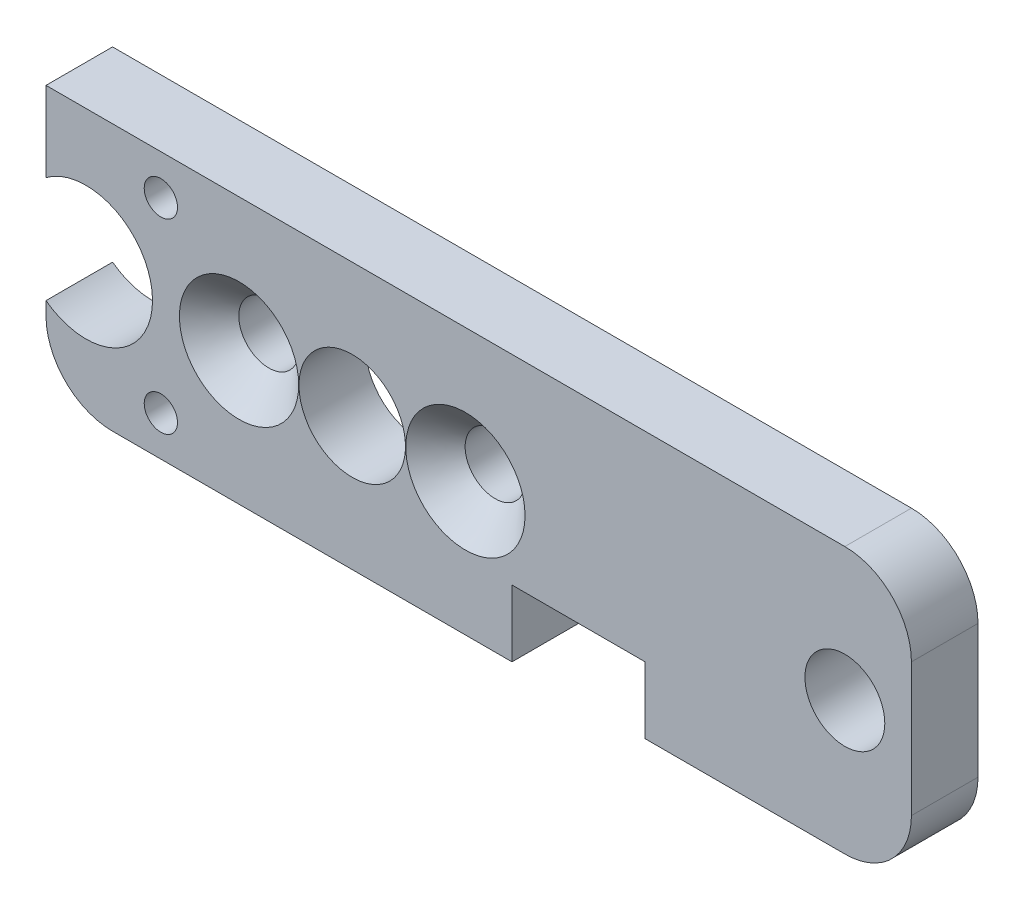
SolidWorks part; units mm, degrees
ref_plane "Front Plane" through (0, 0, 0) normal (0, 0, 1) x (1, 0, 0)
ref_plane "Top Plane" through (0, 0, 0) normal (0, 1, 0) x (1, 0, 0)
ref_plane "Right Plane" through (0, 0, 0) normal (1, 0, 0) x (0, 0, -1)
sketch "Sketch1" plane through (0, 0, 0) normal (0, 0, 1) x (1, 0, 0)
  line L1 (-27.303, 7.4194) -> (37.697, 7.4194)
  line L2 (-27.303, 7.4194) -> (-27.303, -12.5806)
  line L3 (-27.303, -12.5806) -> (37.697, -12.5806)
  line L4 (37.697, 7.4194) -> (37.697, -12.5806)
  dimension "D1" = 65
  dimension "D2" = 20
extrude "Boss-Extrude1" add sketch "Sketch1" along normal blind 5
sketch "Sketch2" plane through (0, 0, 5) normal (0, 0, 1) x (1, 0, 0)
  line L0 (-24.303, -2.5806) -> (-4.303, -2.5806) construction
  line L1 (-27.303, 7.4194) -> (-27.303, -12.5806) construction
  line L2 (-4.303, -2.5806) -> (-10.3134, -8.591) construction
  line L3 (-27.303, -2.5806) -> (-24.303, -2.5806) construction
  line L4 (-4.303, -2.5806) -> (-12.803, -2.5806) construction
  line L5 (-4.303, -2.5806) -> (1.7074, 3.4298) construction
  line L6 (-4.303, -2.5806) -> (4.197, -2.5806) construction
  line L7 (37.697, -2.5806) -> (32.697, -2.5806) construction
  line L8 (37.697, -12.5806) -> (37.697, 7.4194) construction
  dimension "D6" = 8.5
  dimension "D1" = 3
  dimension "D2" = 20
  dimension "D3" = 8.5
  dimension "D4" = 8.5
  dimension "D5" = 8.5
  dimension "D7" = 5
hole_wizard "Ø10.0mm Dowel Hole1" positions "3DSketch2" profile "Sketch4" hole size "Ø10.0" standard "ISO"
sketch3d "3DSketch2"
  point P0 (-24.303, -2.5806, 5)
sketch "Sketch4" plane through (-24.303, -2.5806, 5) normal (1, 0, 0) x (0, -1, 0)
  line L0 (0, 0) -> (0, 28.0043)
  line L1 (0, 28.0043) -> (5, 25)
  line L2 (5, 25) -> (5, 0)
  line L5 (5, 0) -> (0, 0)
  line L10 (0, 28.0043) -> (-5, 25) construction
  line L11 (0, -6.35) -> (0, 107.95) construction
  dimension "Hole Dia." = 10
  dimension "Hole Depth" = 25
  dimension "Drill Angle" = 118
hole_wizard "CSK for M4 Hex Socket Countersunk Cap Screw1" positions "3DSketch5" profile "Sketch8" countersink size "M4" standard "ISO" end condition through all
sketch3d "3DSketch5"
  point P0 (-12.803, -2.5806, 5)
  point P3 (4.197, -2.5806, 5)
sketch "Sketch8" plane through (-12.803, -2.5806, 5) normal (1, 0, 0) x (0, -1, 0)
  line L0 (0, 0) -> (0, 5)
  line L1 (0, 5) -> (2.25, 5)
  line L2 (2.25, 5) -> (2.25, 2.23)
  line L3 (2.25, 2.23) -> (4.48, 0)
  line L5 (4.48, 0) -> (0, 0)
  line L6 (-2.25, 2.23) -> (-4.48, 0) construction
  line L11 (0, -6.35) -> (0, 107.95) construction
  dimension "Thru Hole Dia." = 4.5
  dimension "Thru Hole Depth" = 5
  dimension "Near C'Sink Dia." = 8.96
  dimension "Near C'Sink Angle" = 90
hole_wizard "Ø6.0mm Dowel Hole1" positions "3DSketch6" profile "Sketch9" hole size "Ø6.0" standard "ISO"
sketch3d "3DSketch6"
  point P0 (32.697, -2.5806, 5)
sketch "Sketch9" plane through (32.697, -2.5806, 5) normal (1, 0, 0) x (0, -1, 0)
  line L0 (0, 0) -> (0, 26.8026)
  line L1 (0, 26.8026) -> (3, 25)
  line L2 (3, 25) -> (3, 0)
  line L5 (3, 0) -> (0, 0)
  line L10 (0, 26.8026) -> (-3, 25) construction
  line L11 (0, -6.35) -> (0, 107.95) construction
  dimension "Hole Dia." = 6
  dimension "Hole Depth" = 25
  dimension "Drill Angle" = 118
sketch "Sketch11" plane through (0, 0, 0) normal (0, 0, -1) x (-1, 0, 0)
  line L0 (4.303, -2.5806) -> (4.303, -6.9847) construction
hole_wizard "Ø4.0mm Dowel Hole2" positions "3DSketch8" profile "Sketch13" hole size "Ø4.0" standard "ISO"
sketch3d "3DSketch8"
  point P0 (-4.303, -2.5806, 0)
sketch "Sketch13" plane through (-4.303, -2.5806, 0) normal (1, 0, 0) x (0, 1, 0)
  line L0 (0, 0) -> (0, 26.2017)
  line L1 (0, 26.2017) -> (2, 25)
  line L2 (2, 25) -> (2, 0)
  line L5 (2, 0) -> (0, 0)
  line L10 (0, 26.2017) -> (-2, 25) construction
  line L11 (0, -6.35) -> (0, 107.95) construction
  dimension "Hole Dia." = 4
  dimension "Hole Depth" = 25
  dimension "Drill Angle" = 118
hole_wizard "Ø8.0mm Dowel Hole1" positions "3DSketch9" profile "Sketch14" hole size "Ø8.0" standard "ISO"
sketch3d "3DSketch9"
  point P0 (-4.303, -2.5806, 0)
sketch "Sketch14" plane through (-4.303, -2.5806, 0) normal (1, 0, 0) x (0, 1, 0)
  line L0 (0, 0) -> (0, 7.4034)
  line L1 (0, 7.4034) -> (4, 5)
  line L2 (4, 5) -> (4, 0)
  line L5 (4, 0) -> (0, 0)
  line L10 (0, 7.4034) -> (-4, 5) construction
  line L11 (0, -6.35) -> (0, 107.95) construction
  dimension "Hole Dia." = 8
  dimension "Hole Depth" = 5
  dimension "Drill Angle" = 118
sketch "Sketch22" plane through (0, 0, 0) normal (0, 0, -1) x (-1, 0, 0)
  line L0 (-37.697, -2.5806) -> (-17.697, -2.5806) construction
  line L1 (-17.697, -2.5806) -> (-17.697, -12.5806) construction
  line L2 (27.303, -12.5806) -> (-37.697, -12.5806) construction
  line L3 (-17.697, -12.5806) -> (-17.697, -7.5806)
  line L4 (-17.697, -7.5806) -> (-7.697, -7.5806)
  line L5 (-7.697, -7.5806) -> (-7.697, -12.5806)
  line L6 (-7.697, -12.5806) -> (-17.697, -12.5806)
  dimension "D1" = 20
  dimension "D2" = 5
  dimension "D3" = 10
extrude "Cut-Extrude1" cut sketch "Sketch22" against normal blind 10
sketch "Sketch23" plane through (0, 0, 0) normal (0, 0, -1) x (-1, 0, 0)
  circle A0 centre (4.303, -2.5806) radius 12.5
  circle A1 centre (24.303, -2.5806) radius 5
  dimension "D1" = 25
  dimension "D2" = 10
sketch "Sketch25" plane through (0, -7.5806, 0) normal (0, -1, 0) x (1, 0, 0)
  line L0 (17.697, 2.5) -> (7.697, 2.5) construction
  line L1 (17.697, 5) -> (17.697, 0) construction
  line L2 (7.697, 5) -> (7.697, 0) construction
  line L3 (12.697, 2.5) -> (12.697, 5) construction
  line L4 (17.697, 5) -> (7.697, 5) construction
hole_wizard "M2 Tapped Hole2" positions "3DSketch12" profile "Sketch26" tap size "M2" standard "ISO"
sketch3d "3DSketch12"
  point P0 (12.697, -7.5806, 2.5)
sketch "Sketch26" plane through (12.697, -7.5806, 2.5) normal (1, 0, 0) x (0, 0, -1)
  line L0 (0, 0) -> (0, 7.4807)
  line L1 (0, 7.4807) -> (0.8, 7)
  line L2 (0.8, 7) -> (0.8, 0)
  line L5 (0.8, 0) -> (0, 0)
  line L10 (0, 7.4807) -> (-0.8, 7) construction
  line L11 (0, -6.35) -> (0, 107.95) construction
  dimension "Tap Drill Dia." = 1.6
  dimension "Tap Drill Depth" = 7
  dimension "Drill Angle" = 118
cosmetic thread "Hole Thread1" parameters "D1"=5, "D2"=2
fillet "Fillet1" radius 5 3 edges at (37.697, 7.4194, 2.5) (37.697, -12.5806, 2.5) (-27.303, -12.5806, 2.5)
sketch "Sketch27" plane through (0, 0, 0) normal (0, 0, -1) x (-1, 0, 0)
  line L0 (16.803, -2.5806) -> (16.803, 7.4194) construction
  line L1 (24.303, -2.5806) -> (4.303, -2.5806) construction
  line L2 (-32.697, 7.4194) -> (27.303, 7.4194) construction
  line L3 (27.303, 4.4194) -> (16.803, 4.4194) construction
  line L4 (27.303, 7.4194) -> (27.303, 1.4194) construction
  line L5 (18.6764, 4.4194) -> (18.6764, -2.5806) construction
  line L6 (18.6764, -2.5806) -> (18.6764, -9.5806) construction
  circle A0 centre (4.303, -2.5806) radius 12.5 construction
  dimension "D1" = 7
hole_wizard "M3 Tapped Hole2" positions "3DSketch14" profile "Sketch29" tap size "M3" standard "ISO"
sketch3d "3DSketch14"
  point P0 (-18.6764, 4.4194, 0)
  point P3 (-18.6764, -9.5806, 0)
sketch "Sketch29" plane through (-18.6764, 4.4194, 0) normal (1, 0, 0) x (0, 1, 0)
  line L0 (0, 0) -> (0, 8.2511)
  line L1 (0, 8.2511) -> (1.25, 7.5)
  line L2 (1.25, 7.5) -> (1.25, 0)
  line L5 (1.25, 0) -> (0, 0)
  line L10 (0, 8.2511) -> (-1.25, 7.5) construction
  line L11 (0, -6.35) -> (0, 107.95) construction
  dimension "Tap Drill Dia." = 2.5
  dimension "Tap Drill Depth" = 7.5
  dimension "Drill Angle" = 118
cosmetic thread "Hole Thread5" parameters "D1"=5, "D2"=3
cosmetic thread "Hole Thread6" parameters "D1"=5, "D2"=3
sketch "Sketch32" plane through (0, 0, -105) normal (0, 0, -1) x (-1, 0, 0)
  line L0 (18.6764, -9.5806) -> (26.8856, -9.5806) construction
  arc A0 (22.303, -12.5806) -> (27.303, -7.5806) centre (22.303, -7.5806) ccw construction
